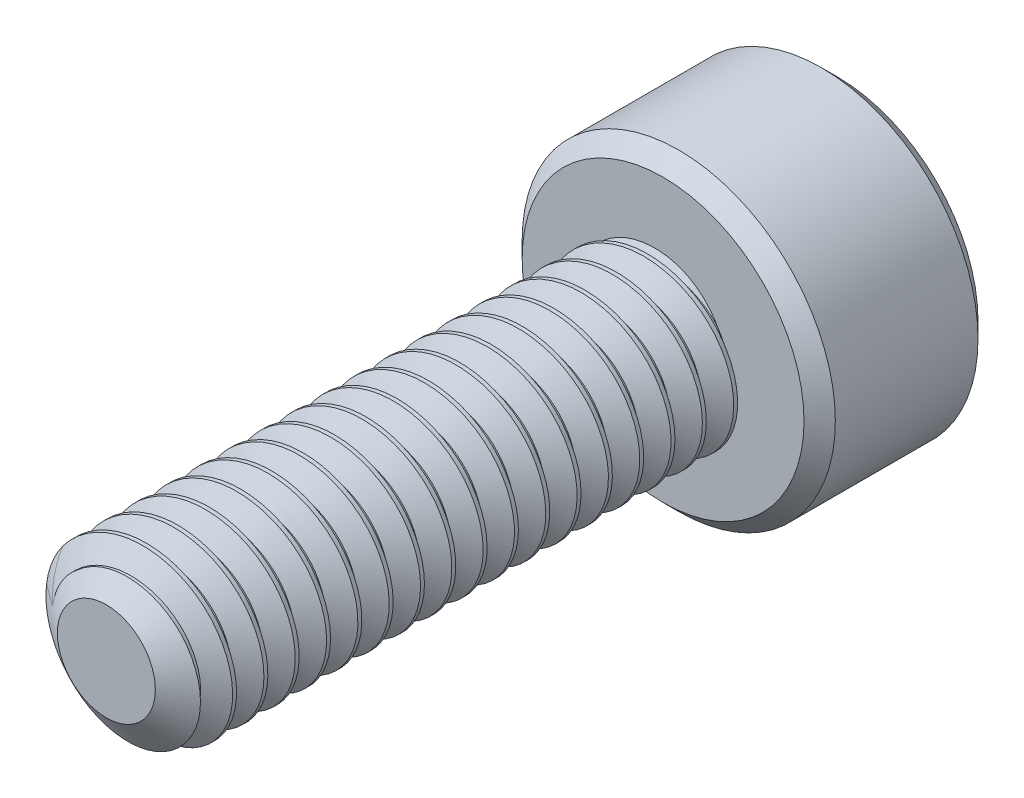
SolidWorks part; units mm, degrees
other "DetailItem1"
ref_plane "Front Plane" through (0, 0, 0) normal (0, 0, 1) x (1, 0, 0)
ref_plane "Top Plane" through (0, 0, 0) normal (0, 1, 0) x (1, 0, 0)
ref_plane "Right Plane" through (0, 0, 0) normal (1, 0, 0) x (0, 0, -1)
sketch "Sketch1" plane through (0, 0, 0) normal (0, 0, 1) x (1, 0, 0)
  circle A0 centre (0, 0) radius 1.25
  dimension "OD" = 2.5
extrude "Extrude1" add sketch "Sketch1" against normal blind 8
sketch "Sketch2" plane through (0, 0, 0) normal (0, 0, 1) x (1, 0, 0)
  circle A0 centre (0, 0) radius 1.25 construction
  circle A1 centre (0, 0) radius 1.25
curve "Helix/Spiral1" pitch 0.45 height 8.45 radius 1.25 centre (0, 0, 0) axis (0, 0, -1) start towards (0, 1, 0) parameters "pitch"=0.45
sketch "Sketch3" plane through (0, 0, 0) normal (1, 0, 0) x (0, 0, -1)
  line L0 (-0.3938, 1.25) -> (-0.225, 0.9577)
  line L1 (-0.225, 0.9577) -> (-0.1688, 0.9577)
  line L2 (-0.1688, 0.9577) -> (0, 1.25)
  line L3 (-0.3938, 1.25) -> (0, 1.25)
  line L4 (-0.1969, 1.25) -> (-0.1969, 0.9577) construction
  line L5 (-0.3094, 1.1039) -> (-0.0844, 1.1039) construction
  line L6 (0, 1.25) -> (0, -1.25) construction
  dimension "D1" = 0.0563
  dimension "D2" = 0.225
  dimension "D3" = 60
sweep "Cut-Sweep1" cut profiles "Sketch3" path "Helix/Spiral1" align with end faces yes
sketch "Sketch4" plane through (0, 0, 0) normal (1, 0, 0) x (0, 0, -1)
  line L0 (0.3825, 1.25) -> (0, 0.7037)
  line L1 (0, 0.7037) -> (0, 1.25)
  line L2 (0.3825, 1.25) -> (0, 1.25)
  line L3 (-0.3938, 1.25) -> (0, 1.25) construction
  line L4 (0, 0) -> (7.0209, 0) construction
  dimension "D1" = 55
  dimension "D2" = 0.254
revolve "Cut-Revolve1" cut sketch "Sketch4" angle 360 about L4
sketch "Sketch6" plane through (0, 0, -8) normal (0, 0, -1) x (-1, 0, 0)
  circle A0 centre (0, 0) radius 2.25
  dimension "head dia" = 4.5
extrude "Extrude2" add sketch "Sketch6" along normal blind 2.5
sketch "Sketch7" plane through (0, 0, -10.5) normal (0, 0, -1) x (-1, 0, 0)
  line L1 (0, 1.1547) -> (-1, 0.5774)
  line L2 (-1, 0.5774) -> (-1, -0.5774)
  line L3 (-1, -0.5774) -> (0, -1.1547)
  line L4 (0, -1.1547) -> (1, -0.5774)
  line L5 (1, -0.5774) -> (1, 0.5774)
  line L6 (1, 0.5774) -> (0, 1.1547)
  circle A0 centre (0, 0) radius 1 construction
  dimension "hex dia" = 2
extrude "Cut-Extrude1" cut sketch "Sketch7" against normal blind 1.5
sketch "Sketch8" plane through (0, 0, -10.5) normal (0, 0, -1) x (-1, 0, 0)
  circle A0 centre (0, 0) radius 1.1547
extrude "Cut-Extrude2" cut sketch "Sketch8" against normal through all draft 45
chamfer "Chamfer1" distance 0.225 angle 45 2 edges at (-2.25, 0, -10.5) (-2.25, 0, -8)
sketch "Sketch10" plane through (0, 0, -8) normal (0, 0, 1) x (1, 0, 0)
  circle A1 centre (0, 0) radius 1.25
  circle A2 centre (0, 0) radius 1.25
  dimension "D1" = 0
ref_plane "Plane1" through (0, 0, 0) normal (0, 0, 1) x (1, 0, 0)
extrude "partial thread" [suppressed] add sketch "Sketch10" along normal up to surface (36 mm away) separate body up to plane "Plane1"
chamfer "Chamfer2" [suppressed] distance 0.05 angle 45
combine bodies "Combine1" [suppressed] operation type add bodies to combine 107 108
sketch "Sketch9" plane through (0, 0, 0) normal (1, 0, 0) x (0, 0, -1)
  line L0 (0, 1.25) -> (0, -1.25) construction
  line L1 (1.125, 1.25) -> (1.125, -1.25) construction
  dimension "D1" = 1.125
equation "\"D3@Helix/Spiral1\" = \"screw length@Extrude1\"+\"pitch@Helix/Spiral1\""
equation "\"D1@Sketch3\" = \"pitch@Helix/Spiral1\"*.125"
equation "\"D2@Sketch3\" = \"pitch@Helix/Spiral1\"*.5"
equation "\"D1@Cut-Extrude1\" = \"hex dia@Sketch7\"*.75"
equation "\"D1@Chamfer1\" = \"head dia@Sketch6\"*.05"
equation "\"D1@Sketch9\" = \"pitch@Helix/Spiral1\"*2.5"
equation "\"D1@Chamfer2\"=\"OD@Sketch1\"*.02"
